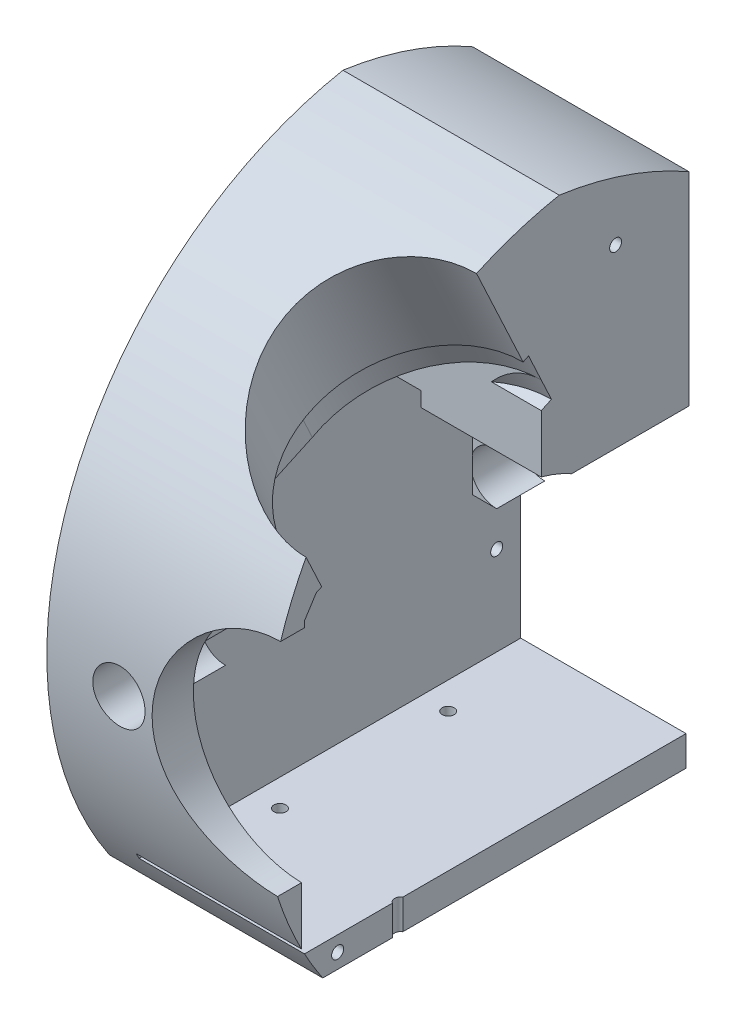
SolidWorks part; units mm, degrees
ref_plane "Front Plane" through (0, 0, 0) normal (0, 0, 1) x (1, 0, 0)
ref_plane "Top Plane" through (0, 0, 0) normal (0, 1, 0) x (1, 0, 0)
ref_plane "Right Plane" through (0, 0, 0) normal (1, 0, 0) x (0, 0, -1)
sketch "Sketch1" plane through (0, 0, 14.8713) normal (0, 0, 1) x (1, 0, 0)
  line L0 (17.8011, 32) -> (17.8011, 29.35)
  line L1 (13.8011, 20.65) -> (13.8011, 19.2554)
  line L2 (13.8011, 20.65) -> (13.8011, -4) construction
  line L3 (13.8011, 20.65) -> (17.8011, 20.65)
  arc A0 (17.8011, 32) -> (13.8011, 19.2554) centre (17.8011, 25) ccw
  arc A1 (22.3161, 30.3493) -> (17.8011, 32) centre (17.8011, 25) ccw construction
  arc A2 (17.8011, 29.35) -> (17.8011, 20.65) centre (17.8011, 25) ccw
extrude "Boss-Extrude1" add sketch "Sketch1" against normal up to surface (10.8581 mm away)
sketch "Sketch2" plane through (0, 0, -49.1287) normal (0, 0, -1) x (-1, 0, 0)
  line L0 (-13.8011, 19.2554) -> (-13.8011, 20.65)
  line L1 (-13.8011, 20.65) -> (-13.8011, -4) construction
  line L2 (-13.8011, 20.65) -> (-17.8011, 20.65)
  line L3 (-17.8011, 32) -> (-17.8011, 29.35)
  arc A0 (-13.8011, 19.2554) -> (-17.8011, 32) centre (-17.8011, 25) ccw
  arc A1 (-17.8011, 20.65) -> (-17.8011, 29.35) centre (-17.8011, 25) ccw
extrude "Boss-Extrude2" add sketch "Sketch2" against normal up to surface (8 mm away) separate body
sketch "Sketch3" plane through (0, 0, 14.8713) normal (0, 0, 1) x (1, 0, 0)
  line L0 (22.3161, 44.5) -> (61.3161, 44.5) construction
  line L1 (13.8011, 44.5) -> (5.8011, 44.5)
  line L3 (13.8011, -4) -> (5.8011, -4)
  line L4 (5.8011, 44.5) -> (5.8011, -4)
  line L5 (41.3161, -4) -> (13.8011, -4) construction
  line L6 (13.8011, 19.2554) -> (13.8011, -4)
  line L7 (22.3161, 30.3493) -> (22.3161, 44.5)
  line L8 (22.3161, 44.5) -> (13.8011, 44.5)
  arc A2 (22.3161, 30.3493) -> (17.8011, 32) centre (17.8011, 25) ccw construction
  arc A4 (22.3161, 30.3493) -> (17.8011, 32) centre (17.8011, 25) ccw
  arc A5 (17.8011, 32) -> (13.8011, 19.2554) centre (17.8011, 25) ccw construction
  arc A6 (17.8011, 32) -> (13.8011, 19.2554) centre (17.8011, 25) ccw
  dimension "D1" = 8
extrude "Boss-Extrude3" add sketch "Sketch3" against normal up to surface (10.8581 mm away)
sketch "Sketch4" plane through (0, 0, -49.1287) normal (0, 0, -1) x (-1, 0, 0)
  line L0 (-13.8011, 20.65) -> (-13.8011, -4) construction
  line L1 (-17.8011, 32) -> (-17.8011, 43.4634) construction
  line L2 (-13.8011, 19.2554) -> (-13.8011, -4)
  line L3 (-17.8011, 32) -> (-17.8011, 43.4634)
  line L4 (-17.8011, 43.4634) -> (-5.8011, 43.4634)
  line L5 (-5.8011, 44.5) -> (-5.8011, -4) construction
  line L6 (-5.8011, 43.4634) -> (-5.8011, -4)
  line L7 (-5.8011, -4) -> (-13.8011, -4)
  arc A0 (-13.8011, 19.2554) -> (-17.8011, 32) centre (-17.8011, 25) ccw construction
  arc A1 (-13.8011, 19.2554) -> (-17.8011, 32) centre (-17.8011, 25) ccw
extrude "Boss-Extrude4" add sketch "Sketch4" against normal up to surface (8 mm away)
sketch "Sketch5" plane through (0, 0, -41.1287) normal (0, 0, 1) x (1, 0, 0)
  line L2 (5.8011, 43.4634) -> (13.8011, 43.4634)
  line L3 (5.8011, 43.4634) -> (5.8011, -4)
  line L4 (5.8011, -4) -> (13.8011, -4)
  line L6 (13.8011, 43.4634) -> (13.8011, -4)
extrude "Boss-Extrude5" add sketch "Sketch5" along normal up to surface (45.1419 mm away) up to face at (14.7818, 23.8221, 4.0131)
sketch "Sketch6" plane through (0, 0, 14.8713) normal (0, 0, 1) x (1, 0, 0)
  line L0 (41.3161, 6.5068) -> (41.3161, -4)
  line L1 (5.8011, 44.5) -> (41.3161, 44.5)
  line L2 (5.8011, 44.5) -> (5.8011, -4)
  line L3 (5.8011, -4) -> (41.3161, -4)
  line L4 (41.3161, 44.5) -> (41.3161, 43.4932)
  circle A0 centre (41.8161, 25) radius 18.5 construction
  arc A1 (41.3161, 43.4932) -> (41.3161, 6.5068) centre (41.8161, 25) ccw
  arc A2 (17.8011, 20.65) -> (17.8011, 29.35) centre (17.8011, 25) ccw construction
  arc A3 (17.8011, 20.65) -> (17.8011, 29.35) centre (17.8011, 25) ccw
  arc A4 (17.8011, 29.35) -> (17.8011, 20.65) centre (17.8011, 25) ccw construction
  arc A5 (17.8011, 29.35) -> (17.8011, 20.65) centre (17.8011, 25) ccw
extrude "Boss-Extrude6" add sketch "Sketch6" along normal blind 10
sketch "Sketch7" plane through (41.8161, 0, 0) normal (-1, 0, 0) x (0, 0, 1)
  line L7 (14.6134, 53.5462) -> (12.0176, 47.9794)
  line L8 (12.0176, 47.9794) -> (12.9239, 47.5568)
  line L9 (12.9239, 47.5568) -> (14.8713, 44.5)
  line L10 (14.8713, 44.5) -> (14.8713, 43.5)
  line L11 (14.8713, 43.5) -> (18.8533, 43.5)
  line L13 (14.6134, 53.5462) -> (12.0176, 47.9794)
  line L14 (12.0176, 47.9794) -> (12.9239, 47.5568)
  line L15 (12.9239, 47.5568) -> (14.8713, 44.5)
  line L16 (14.8713, 44.5) -> (14.8713, 43.5)
  line L17 (14.8713, 43.5) -> (18.8533, 43.5)
  line L20 (-49.1287, 77.2293) -> (-49.1287, 43.4634)
  line L21 (-49.1287, 43.4634) -> (-24.5352, 43.4634)
  line L22 (-24.5352, 43.4634) -> (-24.5352, 59.5074)
  line L23 (-24.5352, 59.5074) -> (-22.4221, 64.0389)
  line L24 (-22.4221, 64.0389) -> (-21.5158, 63.6163)
  line L25 (-21.5158, 63.6163) -> (-13.7602, 80.2483)
  line L27 (-49.1287, 77.2293) -> (-49.1287, 43.4634)
  line L28 (-49.1287, 43.4634) -> (-29.5923, 43.4634)
  line L29 (-24.5352, 45.5265) -> (-24.5352, 59.5074)
  line L30 (-24.5352, 59.5074) -> (-22.4221, 64.0389)
  line L31 (-22.4221, 64.0389) -> (-21.5158, 63.6163)
  line L32 (-21.5158, 63.6163) -> (-13.7602, 80.2483)
  arc A0 (-24.5352, 45.5265) -> (-29.5923, 43.4634) centre (-19.1104, 25) ccw
  arc A1 (18.8533, 43.5) -> (14.6134, 53.5462) centre (-39.0025, 25) ccw
  arc A3 (-27.5348, 84.6493) -> (-49.1287, 77.2293) centre (-19.1104, 25) ccw
  arc A4 (-27.5348, 84.6493) -> (-49.1287, 77.2293) centre (-19.1104, 25) ccw
  arc A21 (18.8533, 43.5) -> (14.6134, 53.5462) centre (-39.0025, 25) ccw
  arc A23 (-13.7602, 80.2483) -> (-27.5348, 84.6493) centre (-39.0025, 25) ccw
  arc A24 (-13.7602, 80.2483) -> (-27.5348, 84.6493) centre (-39.0025, 25) ccw
  dimension "D1" = 0
  dimension "D2" = 0
extrude "Boss-Extrude7" add sketch "Sketch7" along normal up to surface (36.015 mm away) up to face at (5.8011, 27.9878, -6.7481)
sketch "Sketch8" plane through (5.8011, 0, 0) normal (-1, 0, 0) x (0, 0, 1)
  line L0 (14.8713, 44.5) -> (12.9239, 47.5568)
  line L1 (12.9239, 47.5568) -> (12.0176, 47.9794)
  line L2 (12.0176, 47.9794) -> (-24.5352, 47.9794)
  line L3 (-24.5352, 45.5265) -> (-24.5352, 59.5074) construction
  line L4 (-24.5352, 47.9794) -> (-24.5352, 45.5265)
  line L5 (-29.5923, 43.4634) -> (4.0131, 43.4634)
  line L6 (4.0131, 43.4634) -> (4.0131, 44.5)
  line L7 (4.0131, 44.5) -> (14.8713, 44.5)
  arc A0 (-24.5352, 45.5265) -> (-29.5923, 43.4634) centre (-19.1104, 25) ccw construction
  arc A1 (-24.5352, 45.5265) -> (-29.5923, 43.4634) centre (-19.1104, 25) ccw
extrude "Boss-Extrude8" add sketch "Sketch8" against normal up to surface (8 mm away) up to face at (13.8011, 23.4608, -18.9669)
sketch "Sketch9" plane through (13.8011, 0, 0) normal (1, 0, 0) x (0, 0, -1)
  line L0 (-4.0131, 44.5) -> (-4.0131, 47.9794)
  line L17 (-14.8713, 20.65) -> (-14.8713, -4)
  line L18 (-14.8713, -4) -> (49.1287, -4)
  line L19 (49.1287, -4) -> (49.1287, 20.65)
  line L20 (49.1287, 20.65) -> (41.1287, 20.65)
  line L21 (41.1287, 20.65) -> (41.1287, 23.2905)
  line L22 (41.1287, 23.2905) -> (41.1287, 26.7095)
  line L23 (41.1287, 26.7095) -> (41.1287, 43.4634)
  line L24 (41.1287, 43.4634) -> (29.5923, 43.4634)
  line L25 (24.5352, 45.5265) -> (24.5352, 47.9794)
  line L26 (24.5352, 47.9794) -> (-12.0176, 47.9794)
  line L27 (-12.0176, 47.9794) -> (-12.9239, 47.5568)
  line L28 (-12.9239, 47.5568) -> (-14.8713, 44.5)
  line L29 (-14.8713, 44.5) -> (-4.0131, 44.5)
  line L30 (-4.0131, 44.5) -> (-4.0131, 26.7095)
  line L31 (-4.0131, 26.7095) -> (-4.0131, 23.2905)
  line L32 (-4.0131, 23.2905) -> (-4.0131, 20.65)
  line L33 (-4.0131, 20.65) -> (-14.8713, 20.65)
  line L43 (-4.0131, 47.9794) -> (-12.0176, 47.9794)
  line L44 (-12.0176, 47.9794) -> (-12.9239, 47.5568)
  line L45 (-12.9239, 47.5568) -> (-14.8713, 44.5)
  line L46 (-14.8713, 44.5) -> (-4.0131, 44.5)
  arc A1 (29.5923, 43.4634) -> (24.5352, 45.5265) centre (19.1104, 25) ccw
  dimension "D1" = 0
extrude "Boss-Extrude9" add sketch "Sketch9" along normal up to surface (8.515 mm away)
sketch "Sketch11" plane through (13.8011, 0, 0) normal (1, 0, 0) x (0, 0, -1)
  line L0 (24.5352, 47.9794) -> (24.5352, 45.5265)
  line L1 (41.1287, 43.4634) -> (41.1287, 47.9794)
  line L2 (52.7432, 45.6866) -> (52.5609, 45.6856)
  line L3 (41.1287, 47.9794) -> (24.5352, 47.9794)
  line L4 (49.1287, 43.4634) -> (29.5923, 43.4634) construction
  line L5 (41.1287, 43.4634) -> (29.5923, 43.4634)
  arc A0 (29.5923, 43.4634) -> (24.5352, 45.5265) centre (19.1104, 25) ccw construction
  arc A1 (29.5923, 43.4634) -> (24.5352, 45.5265) centre (19.1104, 25) ccw
extrude "Cut-Extrude4" cut sketch "Sketch11" along normal blind 8 contours A1 L0 L3 L1 L5
sketch "Sketch14" plane through (0, 39.4814, 18.4105) normal (0, -0.9063, -0.4226) x (1, 0, 0)
  line L2 (22.3161, -16.6399) -> (13.8011, -16.6399)
  line L3 (13.8011, -16.6399) -> (13.8011, -44.7208)
  line L4 (13.8011, -44.7208) -> (31.9764, -44.7208)
  line L5 (22.3161, -16.6399) -> (22.3448, -26.8287)
  arc A0 (22.3448, -26.8287) -> (61.3161, -27.8854) centre (41.8161, -27.8854) ccw construction
  arc A1 (22.3448, -26.8287) -> (31.9764, -44.7208) centre (41.8161, -27.8854) ccw
extrude "Boss-Extrude19" add sketch "Sketch14" against normal up to surface (5 mm away) separate body
sketch "Sketch15" plane through (0, 20.0259, -42.9457) normal (0, -0.4226, 0.9063) x (1, 0, 0)
  line L4 (5.8011, 48.563) -> (5.8011, 43.563)
  line L5 (5.8011, 43.563) -> (41.8161, 43.563)
  line L6 (41.8161, 43.563) -> (41.8161, 48.563)
  line L7 (41.8161, 48.563) -> (5.8011, 48.563)
  line L8 (5.8011, 48.563) -> (5.8011, 43.563)
  line L9 (5.8011, 43.563) -> (41.8161, 43.563)
  line L10 (41.8161, 43.563) -> (41.8161, 48.563)
  line L11 (41.8161, 48.563) -> (5.8011, 48.563)
  dimension "D1" = 0
extrude "Boss-Extrude21" add sketch "Sketch15" along normal up to surface (2.6646 mm away) separate body up to face at (22.8888, 60.647, -21.0637)
sketch "Sketch16" plane through (5.8011, 0, 0) normal (-1, 0, 0) x (0, 0, 1)
  line L0 (12.0176, 47.9794) -> (-24.5352, 47.9794) construction
  line L1 (-24.5352, 47.9794) -> (-24.5352, 59.5074) construction
  line L2 (-22.1203, 58.3813) -> (-24.5352, 59.5074) construction
  line L3 (3.3297, 46.5137) -> (-22.1203, 58.3813) construction
  line L4 (0.1865, 47.9794) -> (-24.5352, 47.9794)
  line L5 (-24.5352, 47.9794) -> (-24.5352, 59.5074)
  line L6 (-22.1203, 58.3813) -> (-24.5352, 59.5074)
  line L7 (0.1865, 47.9794) -> (-22.1203, 58.3813)
extrude "Boss-Extrude23" add sketch "Sketch16" against normal up to surface (8 mm away) separate body up to face at (13.8011, 54.7133, -8.3388)
sketch "Sketch17" plane through (5.8011, 0, 0) normal (-1, 0, 0) x (0, 0, 1)
  line L0 (-22.1203, 58.3813) -> (0.1865, 47.9794)
  line L1 (0.1865, 47.9794) -> (12.0176, 47.9794)
  line L2 (12.0176, 47.9794) -> (-20.0072, 62.9128)
  line L3 (-20.0072, 62.9128) -> (-22.1203, 58.3813)
extrude "Boss-Extrude25" add sketch "Sketch17" against normal up to surface (8 mm away) separate body up to face at (13.8011, 54.7133, -8.3388)
sketch "Sketch18" plane through (13.8011, 0, 0) normal (1, 0, 0) x (0, 0, -1)
  line L0 (-5.4428, 51.0453) -> (-12.0176, 47.9794)
  line L1 (-12.0176, 47.9794) -> (-4.0131, 47.9794)
  line L2 (-4.0131, 47.9794) -> (-5.4428, 51.0453)
extrude "Boss-Extrude26" add sketch "Sketch18" along normal up to surface (8.4946 mm away) up to face at (22.3305, 50.9325, -0.2309)
sketch "Sketch19" plane through (0, 44.013, 20.5236) normal (0, 0.9063, 0.4226) x (1, 0, 0)
  line L0 (22.3448, 26.8287) -> (61.3161, 27.8854)
  arc A0 (61.3161, 27.8854) -> (22.3448, 26.8287) centre (41.8161, 27.8854) ccw construction
  arc A1 (61.3161, 27.8854) -> (22.3448, 26.8287) centre (41.8161, 27.8854) ccw
extrude "Cut-Extrude5" cut sketch "Sketch19" against normal blind 9
sketch "Sketch20" plane through (0, 44.013, 20.5236) normal (0, 0.9063, 0.4226) x (1, 0, 0)
  line L0 (5.8011, 46.3854) -> (5.8011, 9.3854)
  line L1 (5.8011, 9.3854) -> (22.2957, 9.3854)
  line L2 (22.2957, 9.3854) -> (22.3448, 26.8287)
  line L3 (5.8011, 46.3854) -> (35.6517, 46.3854)
  arc A0 (61.3161, 27.8854) -> (22.3448, 26.8287) centre (41.8161, 27.8854) ccw construction
  arc A1 (35.6517, 46.3854) -> (22.3448, 26.8287) centre (41.8161, 27.8854) ccw
extrude "Boss-Extrude27" add sketch "Sketch20" along normal up to surface (18.3514 mm away) up to face at (23.8086, 82.6544, -20.5818)
sketch "Sketch21" plane through (0, 44.013, 20.5236) normal (0, 0.9063, 0.4226) x (1, 0, 0)
  line L3 (41.8161, 9.3854) -> (22.2957, 9.3854)
  line L4 (22.2957, 9.3854) -> (22.3448, 26.8287)
  line L5 (35.6517, 46.3854) -> (41.8161, 46.3854)
  arc A4 (22.3448, 26.8287) -> (35.6517, 46.3854) centre (41.8161, 27.8854) cw
  arc A5 (41.8161, 9.3854) -> (41.8161, 46.3854) centre (41.8161, 27.8854) cw
  point P7 (0, 0)
  point P8 (0, 0)
  point P9 (0, 0)
  point P10 (0, 0)
  point P16 (0, 0)
extrude "Boss-Extrude28" add sketch "Sketch21" along normal up to surface (6.1422 mm away) up to face at (30.7541, 62.8284, 2.6503)
sketch "Sketch22" plane through (0, -4, 0) normal (0, -1, 0) x (1, 0, 0)
  line L1 (41.3161, 33.6911) -> (5.8011, 33.6911)
  line L2 (41.3161, 33.6911) -> (41.3161, -49.1287)
  line L3 (41.3161, -49.1287) -> (5.8011, -49.1287)
  line L4 (5.8011, 33.6911) -> (5.8011, -49.1287)
extrude "Boss-Extrude29" add sketch "Sketch22" along normal up to surface (5 mm away)
ref_plane "Plane1" through (13.8011, 40.5048, -26.0025) normal (0, -1, 0) x (-1, 0, 0)
sketch "Sketch24" plane through (5.8011, 0, 0) normal (-1, 0, 0) x (0, 0, 1)
  arc A1 (-27.5348, 84.6493) -> (-49.1287, 77.2293) centre (-19.1104, 25) ccw construction
  circle A2 centre (-19.1104, 25) radius 60.2412
  circle A3 centre (-19.1104, 25) radius 106.9512
extrude "Cut-Extrude6" cut sketch "Sketch24" against normal through all
sketch "Sketch25" plane through (0, -9, 0) normal (0, -1, 0) x (1, 0, 0)
  circle A0 centre (41.8161, -1.1287) radius 1
  arc A1 (41.3161, -1.9948) -> (41.3161, -0.2627) centre (41.8161, -1.1287) ccw construction
  circle A2 centre (18.3011, -4.5578) radius 1
  circle A3 centre (18.3011, -32.5578) radius 1
extrude "Cut-Extrude7" cut sketch "Sketch25" against normal blind 10
sketch "Sketch26" plane through (5.8011, 0, 0) normal (-1, 0, 0) x (0, 0, 1)
  circle A0 centre (-39.0025, 25) radius 60.7416
  arc A1 (13.999, -4.6713) -> (-27.5348, 84.6493) centre (-39.0025, 25) ccw construction
  circle A2 centre (-39.0025, 25) radius 88.7029
extrude "Cut-Extrude8" cut sketch "Sketch26" against normal blind 66
sketch "Sketch27" plane through (5.8011, 0, 0) normal (-1, 0, 0) x (0, 0, 1)
  line L0 (-49.1287, 77.2293) -> (-36.9127, 72.7831) construction
  line L1 (11.3318, -9) -> (8.857, -6.5251) construction
  line L2 (-49.1287, -9) -> (-49.1287, 77.2293) construction
  line L3 (11.3318, -9) -> (-49.1287, -9) construction
  line L4 (-41.1287, 19.2554) -> (-49.1287, 2.4) construction
  line L5 (-49.1287, 20.65) -> (-49.1287, -4) construction
  line L6 (-49.1287, 2.4) -> (-41.1287, 2.4) construction
  line L7 (-41.1287, 2.4) -> (-49.1287, 19.2554) construction
  line L8 (-41.1287, 19.2554) -> (-49.1287, 19.2554) construction
  circle A0 centre (-36.9127, 72.7831) radius 1
  circle A1 centre (8.857, -6.5251) radius 1
  circle A2 centre (-45.1287, 10.8277) radius 1
  dimension "D1" = 2
  dimension "D6" = 2
  dimension "D2" = 3.5
  dimension "D3" = 13
  dimension "D4" = 70
  dimension "D5" = 45
extrude "Cut-Extrude9" cut sketch "Sketch27" against normal through all
sketch "Sketch28" plane through (5.8011, 0, 0) normal (-1, 0, 0) x (0, 0, 1)
  circle A0 centre (-45.1287, 10.8277) radius 1.775
  dimension "D1" = 3.55
extrude "Cut-Extrude10" cut sketch "Sketch28" against normal blind 6
sketch "Sketch29" plane through (5.8011, 0, 0) normal (-1, 0, 0) x (0, 0, 1)
  circle A0 centre (8.857, -6.5251) radius 1.775
  circle A1 centre (-36.9127, 72.7831) radius 1.775
  dimension "D1" = 3.55
  dimension "D2" = 3.55
extrude "Cut-Extrude11" cut sketch "Sketch29" against normal blind 31
